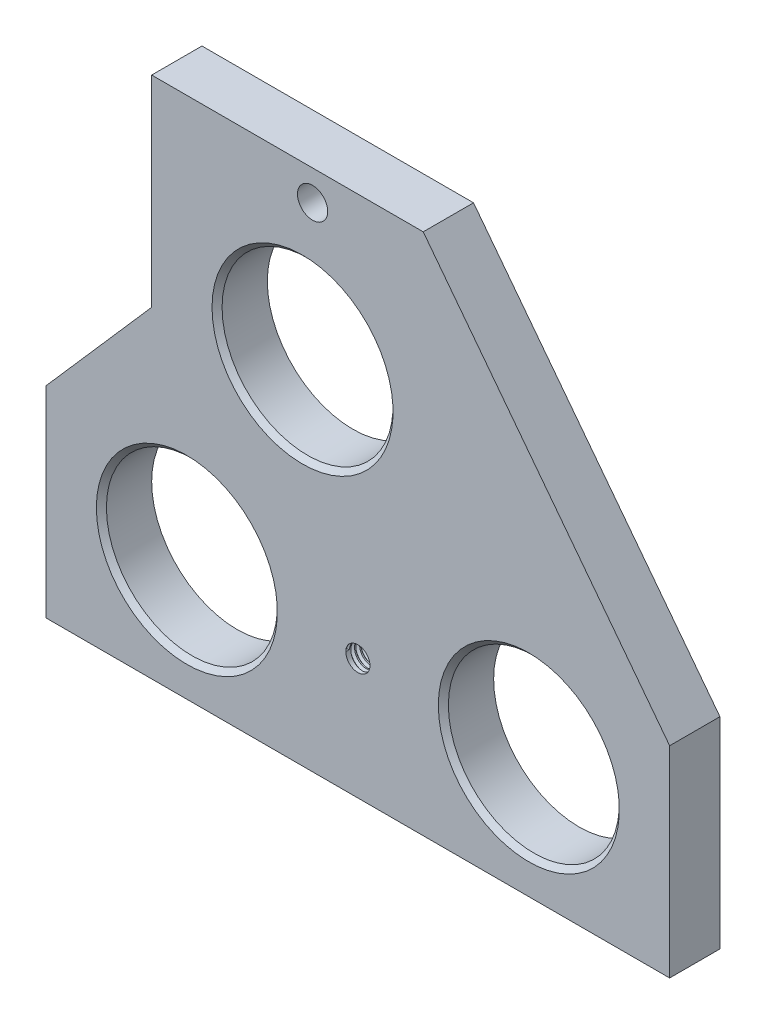
SolidWorks part; units mm, degrees
material "Stop 1060"
ref_plane "Płaszczyzna przednia" through (0, 0, 0) normal (0, 0, 1) x (1, 0, 0)
ref_plane "Płaszczyzna górna" through (0, 0, 0) normal (0, 1, 0) x (1, 0, 0)
ref_plane "Płaszczyzna prawa" through (0, 0, 0) normal (1, 0, 0) x (0, 0, -1)
sketch "Szkic1" plane through (0, 0, 0) normal (0, 0, 1) x (1, 0, 0)
  line L0 (-14, -12) -> (-14, 8)
  line L1 (-3.5, 40) -> (23.5, 40)
  line L2 (48, 8) -> (48, -12)
  line L3 (48, -12) -> (-14, -12)
  line L4 (-3.5, 40) -> (-3.5, 20)
  line L6 (-14, 8) -> (-3.5, 20)
  line L7 (23.5, 40) -> (48, 8)
  circle A0 centre (0, 0) radius 8.5
  circle A1 centre (34, 0) radius 8.5
  circle A2 centre (11.5, 23) radius 8.5
  circle A3 centre (12.5, 37) radius 1.5
  circle A4 centre (17, 0) radius 1.2
  dimension "D1" = 17
  dimension "D2" = 17
  dimension "D3" = 17
  dimension "D4" = 34
  dimension "D5" = 23
  dimension "D6" = 11.5
  dimension "D8" = 14
  dimension "D9" = 14
  dimension "D10" = 3
  dimension "D11" = 12
  dimension "D17" = 3
  dimension "D18" = 16
  dimension "D19" = 3
  dimension "D20" = 17
  dimension "D21" = 23
  dimension "D22" = 2.4
  dimension "D7" = 12
  dimension "D12" = 20
  dimension "D13" = 27
  dimension "D14" = 20
  dimension "D15" = 20
  dimension "D16" = 24.5
extrude "Dodanie-wyciągnięcie1" add sketch "Szkic1" along normal blind 5
chamfer "Sfazowanie2" distance 0.5 angle 45 3 edges at (42.5, 0, 5) (20, 23, 5) (8.5, 0, 5)
thread "Gwint1" pitch 0.5 method cut profile "Profil gwintu1" start angle 0, offset 0, length 10, pitch 0.5, diameter 2.4
ref_plane "Płaszczyzna1" through (15.8, 0, 5) normal (0, -1, 0) x (-1, 0, 0)
sketch "Profil gwintu1" plane through (15.8, 0, 5) normal (0, -1, 0) x (-1, 0, 0)
  line L0 (0, 0) -> (0, 0.5) construction
  line L1 (0, 0) -> (0.2706, 0.1562)
  line L2 (0.2706, 0.1562) -> (0.2706, 0.2187)
  line L3 (0.2706, 0.2187) -> (0, 0.375)
  line L4 (0.2706, 0.1875) -> (0, 0.1875) construction
  line L11 (0, 0) -> (0, 0.375)
  point P2 (0, 0)
  dimension "Pitch" = 0.5
  dimension "Profile_Angle" = 60
  dimension "Profile_Land" = 0.0625
  dimension "Profile_Height" = 0.2706
